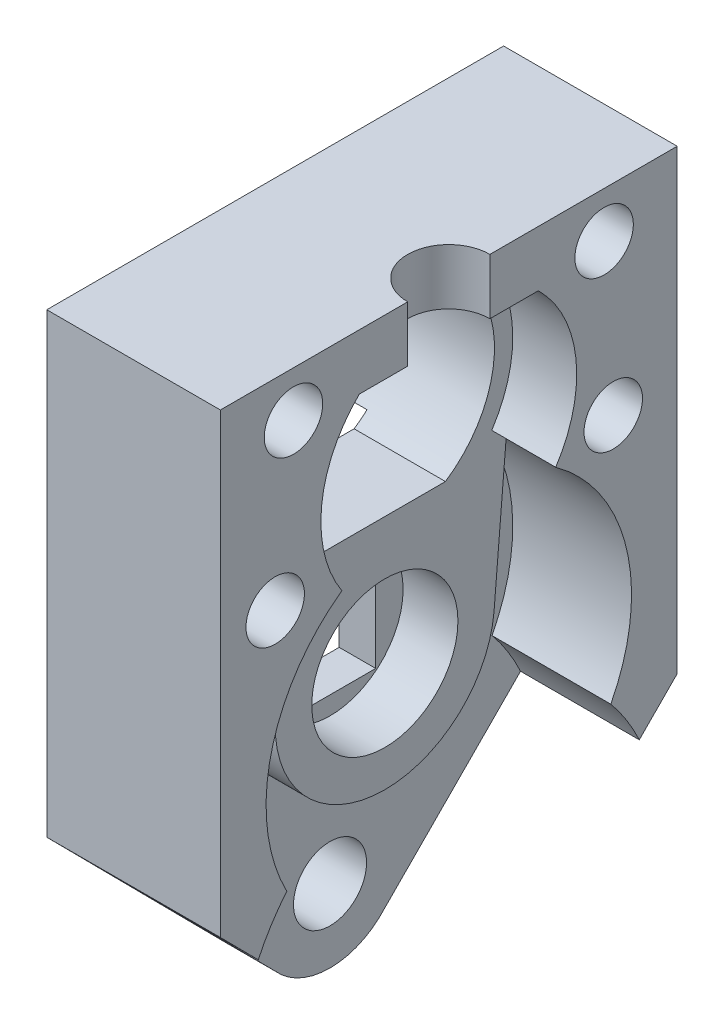
SolidWorks part; units mm, degrees
ref_plane "Front Plane" through (0, 0, 0) normal (0, 0, 1) x (1, 0, 0)
ref_plane "Top Plane" through (0, 0, 0) normal (0, 1, 0) x (1, 0, 0)
ref_plane "Right Plane" through (0, 0, 0) normal (1, 0, 0) x (0, 0, -1)
sketch "Sketch1" plane through (0, 0, 0) normal (1, 0, 0) x (0, 0, -1)
  line L0 (0, -11.95) -> (0, 11.95) construction
  line L2 (-12.5, -5) -> (-12.5, 20)
  line L3 (-12.5, 20) -> (12.5, 20)
  line L4 (12.5, -5) -> (12.5, 20)
  line L8 (-3.3166, 6.95) -> (3.3166, 6.95)
  line L10 (-3.3166, 16.95) -> (3.3166, 16.95)
  line L12 (-3.3166, 6.95) -> (3.3166, 16.95) construction
  line L13 (-3.3166, 16.95) -> (3.3166, 6.95) construction
  line L14 (-2.5, -3) -> (2.5, -3)
  line L15 (-2.5, -3) -> (-2.5, 3)
  line L16 (-2.5, 3) -> (2.5, 3)
  line L17 (2.5, -3) -> (2.5, 3)
  line L18 (-2.5, -3) -> (2.5, 3) construction
  line L19 (-2.5, 3) -> (2.5, -3) construction
  line L20 (-12.5, -5) -> (12.5, -5) construction
  line L25 (12.5, -5) -> (3.0032, -14.5921)
  line L26 (-12.5, -5) -> (-3.0032, -14.5921)
  arc A0 (-3.3166, 16.95) -> (-3.3166, 6.95) centre (0, 11.95) ccw
  arc A1 (3.3166, 6.95) -> (3.3166, 16.95) centre (0, 11.95) ccw
  circle A2 centre (0, -11.95) radius 2
  arc A3 (10.4252, -7.0956) -> (8.8659, -4.6256) centre (0, -11.95) ccw
  arc A6 (-3.0032, -14.5921) -> (3.0032, -14.5921) centre (0, -11.95) ccw
  arc A7 (5.852, 8.1089) -> (-5.852, 8.1089) centre (0, 11.95) ccw
  arc A9 (8.6603, -5) -> (5.852, 8.1089) centre (0, 0) ccw
  arc A10 (-8.8659, -4.6256) -> (-10.4252, -7.0956) centre (0, -11.95) ccw
  arc A11 (-5.852, 8.1089) -> (-8.6603, -5) centre (0, 0) ccw
  point P0 (0, 0)
  point P2 (0, 20)
  point P6 (0, 0)
  point P9 (0, 0)
  point P27 (0, -5)
  dimension "D4" = 11.5
  dimension "D8" = 9.4968
  dimension "D9" = 6.95
  dimension "D11" = 10
  dimension "D13" = 4
  dimension "D15" = 6
  dimension "D5" = 4
  dimension "D6" = 10
  dimension "D7" = 7
  dimension "D12" = 6
  dimension "D1" = 25
  dimension "D2" = 25
  dimension "D3" = 20
  dimension "D10" = 11.95
  dimension "D14" = 5
extrude "Boss-Extrude1" add sketch "Sketch1" along normal blind 9.5 contours A10 A7 A3 L25 L4 L3 L2 L26 | A10 L26 A6 L25 A3 A7 L17 L14 L15 L16 A1 L8 A0 L10 A2 region at (0, 7.5, 12.1313) region at (0, -6.0279, 9.3805)
extrude "Cut-Extrude1" cut sketch "Sketch1<6>" against normal blind 6.5 from surface contours A10 L26 A6 L25 A3 A7 L17 L14 L15 L16 A1 L8 A0 L10 A2 region at (0, -6.0279, 9.3805) starting at face at (9.5, -0.0903, 0)
sketch "Sketch1<6>" plane through (0, 0, 0) normal (1, 0, 0) x (0, 0, -1) same geometry as "Sketch1"
sketch "Sketch2" plane through (0, 0, 0) normal (1, 0, 0) x (0, 0, -1)
  line L0 (-3.3166, 16.95) -> (3.3166, 16.95)
  line L2 (-3.3166, 6.95) -> (3.3166, 6.95)
  line L3 (6.9754, 11.3642) -> (5.979, -0.5021)
  line L4 (0, 11.95) -> (0, 0) construction
  line L5 (-6.9549, 11.1565) -> (-5.9782, -0.5106)
  arc A0 (6.9754, 11.3642) -> (-6.9549, 11.1565) centre (0, 11.95) ccw
  arc A1 (-3.3166, 16.95) -> (-3.3166, 6.95) centre (0, 11.95) ccw
  arc A2 (-5.9782, -0.5106) -> (5.979, -0.5021) centre (0, 0) ccw
  circle A3 centre (0, 0) radius 4
  arc A4 (5.852, 8.1089) -> (-5.852, 8.1089) centre (0, 11.95) ccw construction
  arc A5 (3.3166, 6.95) -> (3.3166, 16.95) centre (0, 11.95) ccw construction
  arc A6 (3.3166, 6.95) -> (3.3166, 16.95) centre (0, 11.95) ccw
  dimension "D1" = 12
  dimension "D2" = 8
extrude "Boss-Extrude2" add sketch "Sketch2" along normal blind 3 from surface starting at face at (3, 0, 0)
sketch "Sketch4" plane through (0, 0, 0) normal (1, 0, 0) x (0, 0, -1)
  line L0 (-4.899, 16.95) -> (4.899, 16.95)
  line L2 (-3.3166, 16.95) -> (3.3166, 16.95) construction
  arc A0 (4.899, 16.95) -> (-4.899, 16.95) centre (0, 11.95) ccw
  arc A1 (5.852, 8.1089) -> (-5.852, 8.1089) centre (0, 11.95) ccw construction
  point P6 (0, 16.95)
extrude "Boss-Extrude3" add sketch "Sketch4" along normal up to surface (9.5 mm away) from surface up to face at (9.5, 3.4839, 0) starting at face at (6, 11.95, 0)
sketch "Sketch3" plane through (0, 0, 0) normal (0, 1, 0) x (1, 0, 0)
  line L0 (9.5, -12.5) -> (9.5, 12.5) construction
  circle A0 centre (9.5, 0) radius 2.25
  dimension "D1" = 4.5
extrude "Cut-Extrude2" cut sketch "Sketch3" along normal blind 7 from surface starting at face at (5.375, 16.95, 0)
sketch "Sketch5" plane through (0, 0, 0) normal (1, 0, 0) x (0, 0, -1)
  line L0 (12.5, -5) -> (12.5, 20) construction
  line L1 (2.25, 20) -> (12.5, 20) construction
  line L2 (-12.5, 20) -> (-2.25, 20) construction
  line L3 (-12.5, -5) -> (-12.5, 20) construction
  circle A0 centre (8.5, 17.5) radius 1.6
  circle A1 centre (-8.5, 17.5) radius 1.6
  circle A2 centre (9, 9) radius 1.6
  circle A3 centre (-9.5, 9) radius 1.6
  dimension "D1" = 2.5
  dimension "D2" = 11
  dimension "D3" = 3.5
  dimension "D4" = 3.2
  dimension "D5" = 3
  dimension "D6" = 4
  dimension "D7" = 4
extrude "Cut-Extrude3" cut sketch "Sketch5" along normal blind 10
sketch "Sketch6" plane through (0, 0, 0) normal (1, 0, 0) x (0, 0, -1)
  line L1 (8.5, -7.5) -> (-8.5, -7.5)
  line L2 (8.5, -7.5) -> (8.5, 7.5)
  line L3 (8.5, 7.5) -> (-8.5, 7.5)
  line L4 (-8.5, -7.5) -> (-8.5, 7.5)
  line L5 (8.5, -7.5) -> (-8.5, 7.5) construction
  line L6 (8.5, 7.5) -> (-8.5, -7.5) construction
  point P0 (0, 0)
  dimension "D1" = 15
  dimension "D2" = 17
extrude "Cut-Extrude4" cut sketch "Sketch6" along normal blind 1 from surface starting at face at (0, 17.5, 6.9)
